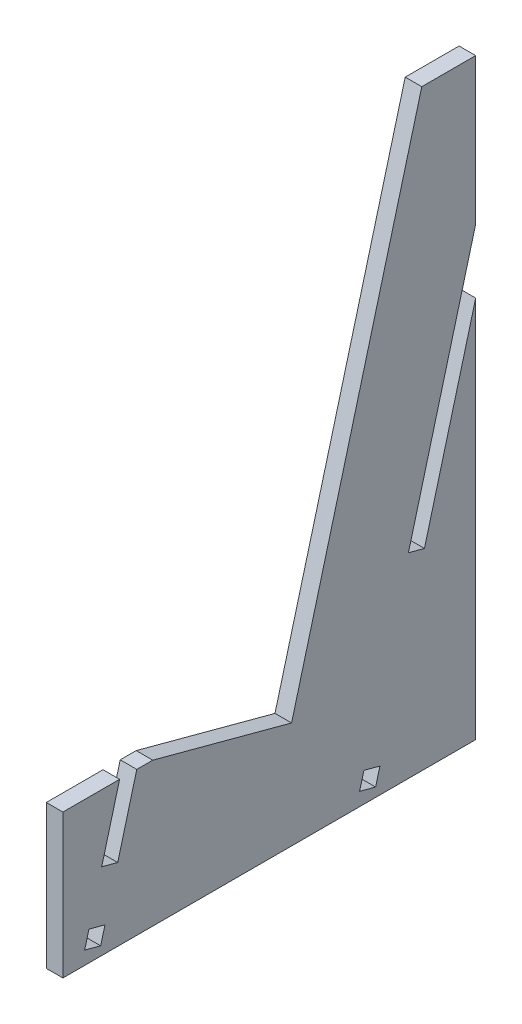
SolidWorks part; units mm, degrees
ref_plane "Front Plane" through (0, 0, 0) normal (0, 0, 1) x (1, 0, 0)
ref_plane "Top Plane" through (0, 0, 0) normal (0, 1, 0) x (1, 0, 0)
ref_plane "Right Plane" through (0, 0, 0) normal (1, 0, 0) x (0, 0, -1)
sketch "Sketch1" plane through (0, 0, 0) normal (1, 0, 0) x (0, 0, -1)
  line L6 (0, 0) -> (0, 104.6968)
  line L7 (0, 104.6968) -> (-9.525, 104.6968)
  line L8 (-9.525, 104.6968) -> (-32.534, 18.826)
  line L9 (-32.534, 18.826) -> (-57.0685, 25.4)
  line L10 (-57.0685, 25.4) -> (-72.9435, 25.4)
  line L11 (-72.9435, 25.4) -> (-72.9435, 0)
  line L12 (-72.9435, 0) -> (0, 0)
  dimension "D1" = 25.4
  dimension "D2" = 15
  dimension "D3" = 88.9
  dimension "D4" = 25.4
  dimension "D5" = 9.525
  dimension "D6" = 15.875
extrude "Boss-Extrude1" add sketch "Sketch1" along normal blind 2.93
sketch "Sketch2" plane through (2.93, 0, 0) normal (1, 0, 0) x (0, 0, -1)
  line L0 (-57.0685, 25.4) -> (-72.9435, 25.4) construction
  line L1 (-69.7685, 25.4) -> (-66.8385, 25.4)
  line L2 (-69.7685, 25.4) -> (-69.7685, 12.7)
  line L3 (-69.7685, 12.7) -> (-66.8385, 12.7)
  line L4 (-66.8385, 25.4) -> (-66.8385, 12.7)
  line L5 (-72.9435, 25.4) -> (-72.9435, 0) construction
  line L6 (-72.9435, 25.4) -> (-72.9435, 0)
  point P8 (-72.9435, 12.7)
  line M11 (-57.0685, 25.4) -> (-72.9435, 25.4)
  dimension "D1" = 2.93
  dimension "D2" = 3.175
extrude "Cut-Extrude1" [suppressed] cut sketch "Sketch2" against normal through all contours L4 L2 L3 M11
sketch "Sketch3" plane through (2.93, 0, 0) normal (1, 0, 0) x (0, 0, -1)
  line L1 (0, 0) -> (-2.93, 0)
  line L2 (0, 0) -> (0, 10)
  line L3 (0, 10) -> (-2.93, 10)
  line L4 (-2.93, 0) -> (-2.93, 10)
  dimension "D1" = 2.93
  dimension "D2" = 10
extrude "Cut-Extrude2" [suppressed] cut sketch "Sketch3" against normal through all
pattern_linear "LPattern1" [suppressed] count 7 spacing 20 of bodies 103
sketch "Sketch4" plane through (2.93, 0, 0) normal (1, 0, 0) x (0, 0, -1)
  line L0 (0, 0) -> (0, 104.6968) construction
  line L1 (0, 10) -> (-2.93, 10)
  line L2 (0, 10) -> (0, 20)
  line L3 (0, 20) -> (-2.93, 20)
  line L4 (-2.93, 10) -> (-2.93, 20)
  line L5 (-72.9435, 0) -> (0, 0) construction
  dimension "D1" = 10
  dimension "D2" = 2.93
  dimension "D3" = 10
extrude "Cut-Extrude3" [suppressed] cut sketch "Sketch4" against normal through all
pattern_linear "LPattern2" [suppressed] count 7 spacing 20 of bodies 105
sketch "Sketch5" plane through (2.93, 0, 0) normal (1, 0, 0) x (0, 0, -1)
  line L0 (0, 78.9083) -> (-11.8852, 34.5522)
  line L1 (0, 78.9083) -> (2.8302, 78.15)
  line L2 (-11.8852, 34.5522) -> (-9.055, 33.7938)
  line L3 (2.8302, 78.15) -> (-9.055, 33.7938)
  line L4 (0, 78.9083) -> (-9.055, 33.7938) construction
  line L5 (-11.8852, 34.5522) -> (2.8302, 78.15) construction
  line L6 (-9.525, 104.6968) -> (-32.534, 18.826) construction
  line L7 (0, 0) -> (0, 104.6968) construction
  line L8 (0, 0) -> (0, 67.5876)
  point P1 (-4.5275, 56.3511)
  point P3 (0, 33.7938)
  line M7 (0, 0) -> (0, 104.6968)
  dimension "D1" = 2.93
  dimension "D2" = 15.875
extrude "Cut-Extrude4" cut sketch "Sketch5" against normal through all contours L3 L0 L2 M7 region at (2.93, 53.8465, 5.2669)
sketch "Sketch6" plane through (0, 0, 0) normal (-1, 0, 0) x (0, 0, 1)
  line L1 (72.9435, 0) -> (70.0135, 0)
  line L2 (72.9435, 0) -> (72.9435, 10)
  line L3 (72.9435, 10) -> (70.0135, 10)
  line L4 (70.0135, 0) -> (70.0135, 10)
  dimension "D1" = 10
  dimension "D2" = 2.93
extrude "Cut-Extrude5" [suppressed] cut sketch "Sketch6" against normal through all
pattern_linear "LPattern3" [suppressed] count 2 spacing 20 of bodies 108
sketch "Sketch7" plane through (0, 0, 0) normal (-1, 0, 0) x (0, 0, 1)
  line L0 (60.2435, 24.0775) -> (66.2697, 1.5875) construction
  line L1 (60.2435, 24.0775) -> (63.0737, 24.8358) construction
  line L2 (66.2697, 1.5875) -> (69.0999, 2.3458) construction
  line L3 (63.0737, 24.8358) -> (69.0999, 2.3458) construction
  line L4 (60.2435, 24.0775) -> (69.0999, 2.3458) construction
  line L5 (66.2697, 1.5875) -> (63.0737, 24.8358) construction
  line L6 (9.525, 104.6968) -> (32.534, 18.826) construction
  line L7 (63.2566, 12.8325) -> (66.0868, 13.5908)
  line L8 (72.9435, 0) -> (0, 0) construction
  line L9 (63.2566, 12.8325) -> (59.8892, 25.4)
  line L10 (66.0868, 13.5908) -> (62.7193, 26.1583)
  line L11 (59.8892, 25.4) -> (62.7193, 26.1583)
  line L12 (57.0685, 25.4) -> (72.9435, 25.4) construction
  point P1 (64.6717, 13.2117)
  dimension "D2" = 2.93
  dimension "D1" = 3.175
  dimension "D3" = 23.2833
  dimension "D4" = 1.5875
extrude "Cut-Extrude6" cut sketch "Sketch7" against normal through all
sketch "Sketch9" plane through (0, 0, 0) normal (-1, 0, 0) x (0, 0, 1)
  line L0 (66.2697, 1.5875) -> (69.0999, 2.3458) construction
  line L1 (66.2697, 1.5875) -> (69.0999, 2.3458)
  line L2 (66.2697, 1.5875) -> (69.0999, 2.3458)
  line L3 (66.2697, 1.5875) -> (65.5114, 4.4177)
  line L4 (69.0999, 2.3458) -> (68.3415, 5.176)
  line L5 (65.5114, 4.4177) -> (68.3415, 5.176)
extrude "Cut-Extrude7" cut sketch "Sketch9" against normal through all contours L5 L3 L1 L4 region at (0, 3.3818, 67.3056)
fillet "Fillet1" [suppressed] radius 0.5
fillet "Fillet2" [suppressed] radius 1
sketch "Sketch11" plane through (0, 0, 0) normal (-1, 0, 0) x (0, 0, 1)
  line L0 (17.6834, 1.5923) -> (20.5136, 2.3506)
  line L1 (17.6834, 1.5923) -> (16.9251, 4.4224)
  line L2 (20.5136, 2.3506) -> (19.7552, 5.1808)
  line L3 (16.9251, 4.4224) -> (19.7552, 5.1808)
  line L4 (11.8852, 34.5522) -> (9.055, 33.7938) construction
  line L6 (0, 67.5876) -> (9.055, 33.7938) construction
  line L7 (0, 78.9083) -> (11.8852, 34.5522) construction
  dimension "D2" = 2.93
  dimension "D1" = 33.3375
extrude "Cut-Extrude9" cut sketch "Sketch11" against normal through all
equation "\"thick\"= 2.93mm'Acrylic thickness"
equation "\"D1@Boss-Extrude1\"=\"thick\""
equation "\"D1@Sketch2\"=\"thick\""
equation "\"slot\"= 10mm'Slot width"
equation "\"D1@Sketch3\"=\"thick\""
equation "\"D2@Sketch3\"=\"slot\""
equation "\"D3@LPattern1\"=2*\"slot\""
equation "\"D1@Sketch4\"=\"slot\""
equation "\"D2@Sketch4\"=\"thick\""
equation "\"D3@Sketch4\"=\"slot\""
equation "\"D3@LPattern2\"=2*\"slot\""
equation "\"D1@Sketch5\"=\"thick\""
equation "\"D1@Sketch6\"=\"slot\""
equation "\"D2@Sketch6\"=\"thick\""
equation "\"D3@LPattern3\"=2 * \"slot\""
equation "\"D2@Sketch7\"=\"thick\""
equation "\"D2@Sketch11\"=\"thick\""
